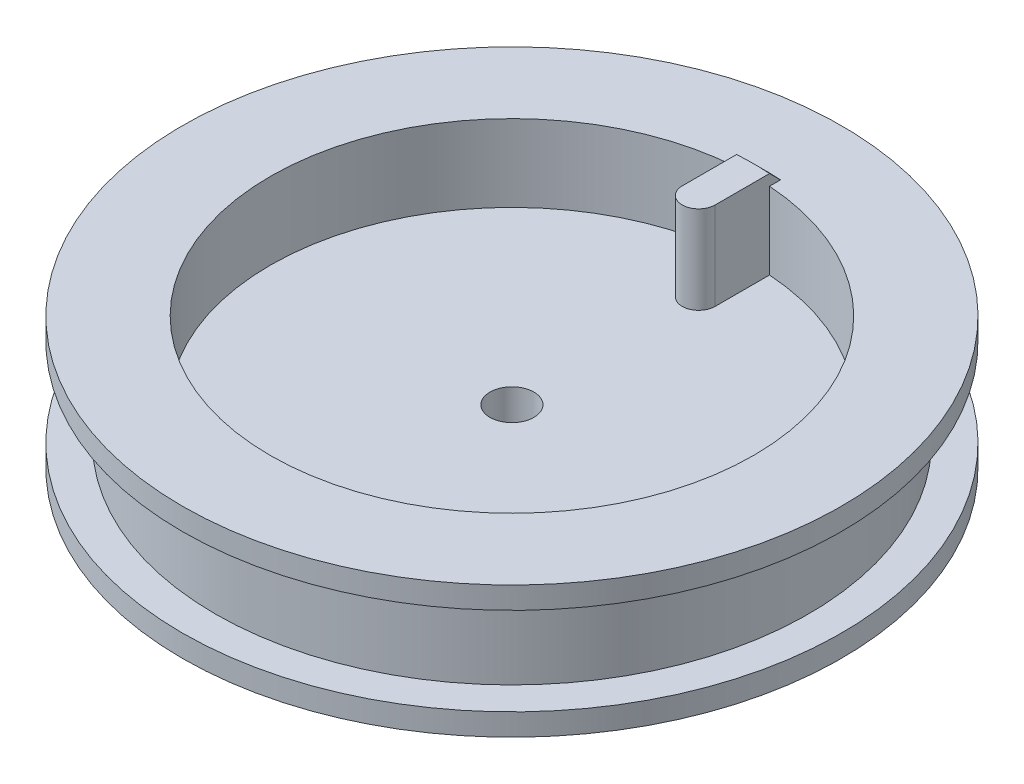
SolidWorks part; units mm, degrees
ref_plane "Front Plane" through (0, 0, 0) normal (0, 0, 1) x (1, 0, 0)
ref_plane "Top Plane" through (0, 0, 0) normal (0, 1, 0) x (1, 0, 0)
ref_plane "Right Plane" through (0, 0, 0) normal (1, 0, 0) x (0, 0, -1)
sketch "Sketch1" plane through (0, 0, 0) normal (0, 1, 0) x (1, 0, 0)
  circle A0 centre (0, 0) radius 30
  circle A1 centre (0, 0) radius 2
  circle A2 centre (0, 0) radius 27
  dimension "D1" = 4
  dimension "D2" = 60
  dimension "D3" = 3
extrude "Boss-Extrude1" add sketch "Sketch1" along normal blind 2 contours A0 A2 | A2 A1 region at (-29.1515, 0, 0) region at (-26.2363, 0, 0)
extrude "Boss-Extrude2" add sketch "Sketch1<3>" along normal blind 8 from surface contours A1 | A2 region at (0, 0, 0) starting at face at (0, 2, 30)
sketch "Sketch1<3>" plane through (0, 0, 0) normal (0, 1, 0) x (1, 0, 0) same geometry as "Sketch1"
sketch "Sketch8" plane through (0, 10, 0) normal (0, 1, 0) x (1, 0, 0)
  line L0 (0, 0) -> (22, 0) construction
  circle A0 centre (0, 0) radius 22
  dimension "D1" = 22
extrude "Cut-Extrude3" cut sketch "Sketch8" against normal offset from surface (5 mm away) 5 up to face at (0, 0, 30)
sketch "Sketch9" plane through (0, 5, 0) normal (0, 1, 0) x (1, 0, 0)
  line L0 (0, 0) -> (0, 17) construction
  line L1 (-1.5, 17) -> (-1.5, 21.9488)
  line L2 (1.5, 17) -> (1.5, 21.9488)
  arc A0 (1.5, 17) -> (-1.5, 17) centre (0, 17) cw
  circle A1 centre (0, 0) radius 22 construction
  circle A2 centre (0, 0) radius 22
  circle M5 centre (0, 0) radius 22
  dimension "D1" = 3
  dimension "D2" = 17
extrude "Boss-Extrude6" add sketch "Sketch9" along normal blind 8 contours A0 L2 L1 M5 region at (0, 5, -18.8933)
sketch "Sketch10" plane through (0, 10, 0) normal (0, 1, 0) x (1, 0, 0)
  circle A0 centre (0, 0) radius 30 construction
  circle A1 centre (0, 0) radius 30
  circle A2 centre (0, 0) radius 22
  arc A3 (-1.5, 21.9488) -> (1.5, 21.9488) centre (0, 0) ccw construction
extrude "Boss-Extrude7" add sketch "Sketch10" along normal blind 2
chamfer "Chamfer3" distance 1 angle 45 1 edges at (0, 12, -22)
